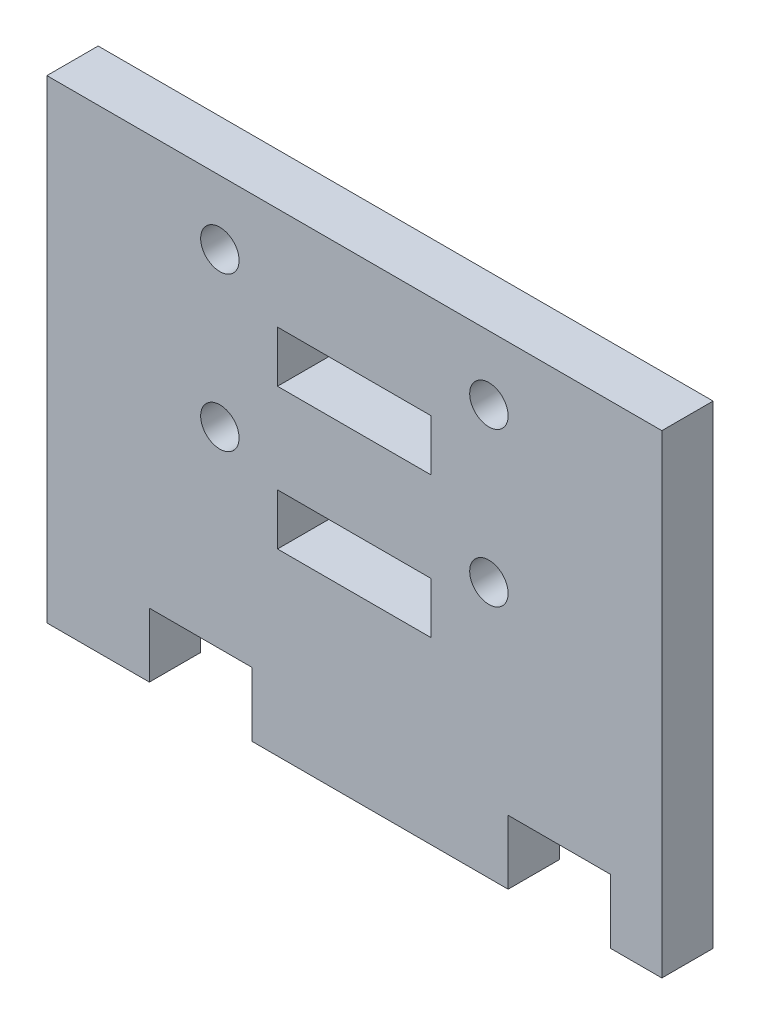
SolidWorks part; units mm, degrees
ref_plane "Front Plane" through (0, 0, 0) normal (0, 0, 1) x (1, 0, 0)
ref_plane "Top Plane" through (0, 0, 0) normal (0, 1, 0) x (1, 0, 0)
ref_plane "Right Plane" through (0, 0, 0) normal (1, 0, 0) x (0, 0, -1)
sketch "Sketch1" plane through (0, 0, 0) normal (0, 0, 1) x (1, 0, 0)
  line L0 (5, 2) -> (9, 2)
  line L1 (5, -0.5) -> (1, -0.5)
  line L2 (1, 18) -> (25, 18)
  line L3 (1, -0.5) -> (1, 18)
  line L4 (10, 14) -> (10, 12)
  line L5 (16, 14) -> (10, 14)
  line L6 (10, 12) -> (16, 12)
  line L7 (16, 12) -> (16, 14)
  line L8 (5, 2) -> (5, -0.5)
  line L9 (23, -0.5) -> (25, -0.5)
  line L10 (25, -0.5) -> (25, 18)
  line L11 (19, -0.5) -> (19, 2)
  line L12 (16, 6.5) -> (16, 8.5)
  line L13 (10, 6.5) -> (16, 6.5)
  line L14 (23, 2) -> (23, -0.5)
  line L15 (16, 8.5) -> (10, 8.5)
  line L16 (10, 8.5) -> (10, 6.5)
  line L17 (19, 2) -> (23, 2)
  line L18 (9, -0.5) -> (9, 2)
  line L19 (9, -0.5) -> (19, -0.5)
  circle A0 centre (7.75, 15.5) radius 0.75
  circle A1 centre (18.25, 15.5) radius 0.75
  circle A2 centre (18.25, 9.5) radius 0.75
  circle A3 centre (7.75, 9.5) radius 0.75
  dimension "D2" = 1.5
  dimension "D3" = 1.5
  dimension "D4" = 1.5
  dimension "D5" = 1.5
  dimension "D6" = 10.5
  dimension "D7" = 6
  dimension "D8" = 6
  dimension "D9" = 6
  dimension "D10" = 1.5
  dimension "D11" = 2.5
  dimension "D12" = 4
  dimension "D13" = 2
  dimension "D14" = 24
  dimension "D15" = 18.5
  dimension "D16" = 10
  dimension "D17" = 4
  dimension "D18" = 2.5
  dimension "D19" = 3.5
  dimension "D20" = 2
  dimension "D21" = 6
  dimension "D22" = 2
  dimension "D23" = 4
  dimension "D24" = 4
  dimension "D25" = 2.5
extrude "Boss-Extrude1" add sketch "Sketch1" along normal blind 2
